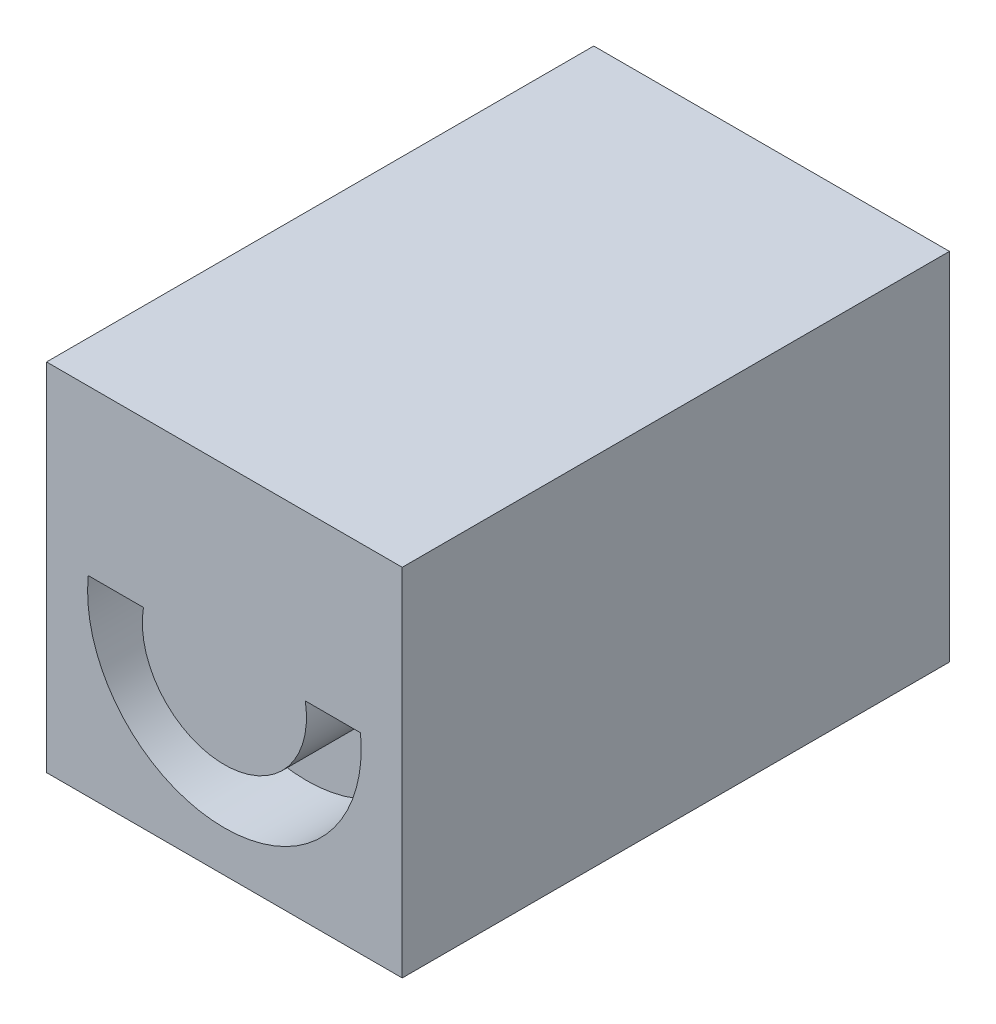
SolidWorks part; units mm, degrees
ref_plane "정면" through (0, 0, 0) normal (0, 0, 1) x (1, 0, 0)
ref_plane "윗면" through (0, 0, 0) normal (0, 1, 0) x (1, 0, 0)
ref_plane "우측면" through (0, 0, 0) normal (1, 0, 0) x (0, 0, -1)
ref_axis "기준축2" through (0, 0, 210) along (0, 0, -1)
ref_axis "기준축4" through (0, 55, 0) along (0, -1, 0)
sketch "스케치1" plane through (0, 0, 0) normal (0, 1, 0) x (1, 0, 0)
  line L0 (40, -7.5) -> (40, 7.5) construction
  line L1 (35, -7.5) -> (45, -7.5)
  line L2 (35, -7.5) -> (35, 7.5)
  line L3 (35, 7.5) -> (45, 7.5)
  line L4 (45, -7.5) -> (45, 7.5)
  point P4 (35, 0)
  dimension "D1" = 15
  dimension "D2" = 10
  dimension "D3" = 40
revolve "회전1" [suppressed] add sketch "스케치1" angle 360 about axis through (0, 0, 210) along (0, 0, -1)
sketch "스케치3" plane through (0, 0, 0) normal (0, 0, 1) x (1, 0, 0)
  line L1 (-78.5289, 68.729) -> (72.7936, 68.729)
  line L2 (-78.5289, 68.729) -> (-78.5289, 0)
  line L3 (-78.5289, 0) -> (72.7936, 0)
  line L4 (72.7936, 68.729) -> (72.7936, 0)
extrude "컷-돌출1" [suppressed] cut sketch "스케치3" against normal mid plane 30
sketch "스케치4" plane through (0, 0, 0) normal (0, 0, 1) x (1, 0, 0)
  line L0 (-49.7494, 5) -> (49.7494, 5)
  line L1 (-65, 65) -> (65, 65)
  line L2 (-65, 65) -> (-65, -65)
  line L3 (-65, -65) -> (65, -65)
  line L4 (65, 65) -> (65, -65)
  circle A0 centre (0, 0) radius 35 construction
  circle A1 centre (0, 0) radius 50
  circle A2 centre (0, 0) radius 45 construction
  circle A5 centre (0, 0) radius 30
  point P4 (0, 65)
  point P6 (65, 0)
  dimension "D3" = 5
  dimension "D4" = 5
  dimension "D6" = 90
  dimension "D7" = 70
  dimension "D1" = 130
  dimension "D2" = 130
  dimension "D5" = 5
extrude "보스-돌출1" add sketch "스케치4" along normal blind 200 separate body contours L4 L1 L2 L3 A1 | L0 A5 | A5 L0 A1 | L0 A5 region at (0, 48.908, 0) region at (0, 15.474, 0) region at (0, -10.0771, 0) region at (0, 63.1615, 0)
sketch "스케치5" plane through (0, 0, 0) normal (0, 0, -1) x (-1, 0, 0)
  line L1 (-65, 65) -> (65, 65)
  line L2 (-65, 65) -> (-65, -65)
  line L3 (-65, -65) -> (65, -65)
  line L4 (65, 65) -> (65, -65)
extrude "보스-돌출2" add sketch "스케치5" against normal offset from surface (170 mm away) 30 up to face at (0, -17.5, 200)
